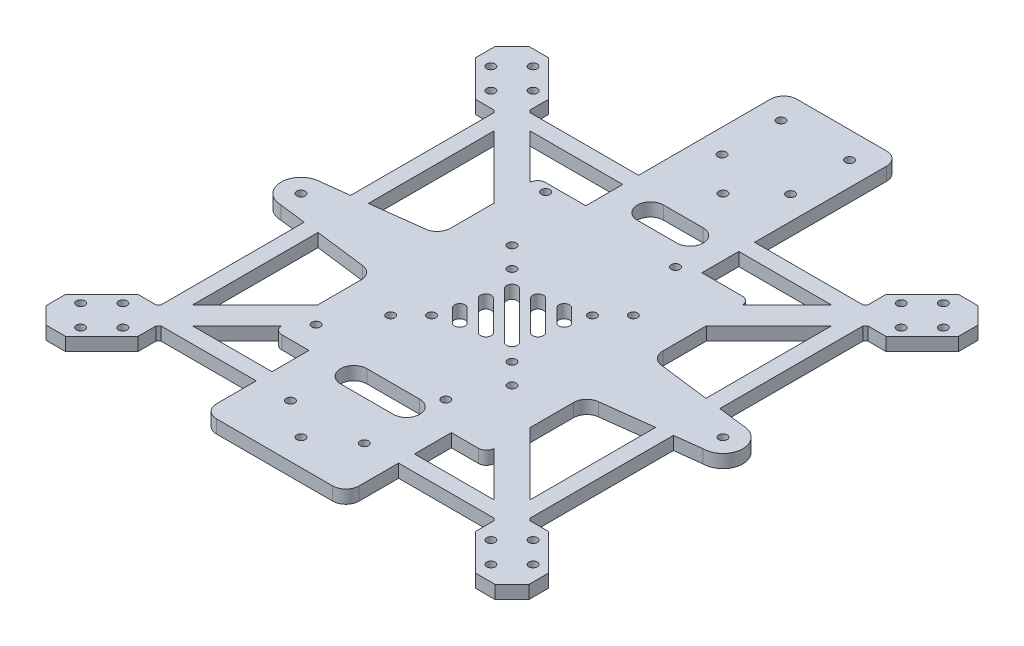
SolidWorks part; units mm, degrees
material "3k碳纤维板"
ref_plane "前视基准面" through (0, 0, 0) normal (0, 0, 1) x (1, 0, 0)
ref_plane "上视基准面" through (0, 0, 0) normal (0, 1, 0) x (1, 0, 0)
ref_plane "右视基准面" through (0, 0, 0) normal (1, 0, 0) x (0, 0, -1)
other "Configuration Table"
sketch "草图1" plane through (0, 0, 0) normal (0, 1, 0) x (1, 0, 0)
  line L0 (-40.28, 0) -> (40.28, 0) construction
  line L1 (-40.28, -50) -> (40.28, -50)
  line L2 (-40.28, -50) -> (-40.28, -16.9164)
  line L3 (-40.28, 50) -> (40.28, 50)
  line L4 (40.28, -50) -> (40.28, -16.9164)
  line L5 (-40.28, -50) -> (40.28, 50) construction
  line L6 (-40.28, 50) -> (40.28, -50) construction
  line L7 (0, -50) -> (0, 50) construction
  line L8 (-40.28, -50) -> (-40.28, -90) construction
  line L9 (-40.28, -90) -> (40.28, -90) construction
  line L10 (40.28, -90) -> (40.28, -50) construction
  line L11 (0, -50) -> (0, -90) construction
  line L12 (-40.28, -70) -> (40.28, -70) construction
  line L13 (-27, -90) -> (27, -90)
  line L14 (27, -90) -> (27, -50)
  line L15 (-27, -90) -> (-27, -50)
  line L16 (44.6626, 11.9547) -> (80, 7.5578)
  line L17 (44.6626, -11.9547) -> (80, -7.5578)
  line L18 (-44.6626, -11.9547) -> (-80, -7.5578)
  line L19 (-44.6626, 11.9547) -> (-80, 7.5578)
  line L20 (40.28, 16.9164) -> (40.28, 50)
  line L21 (-40.28, 16.9164) -> (-40.28, 50)
  circle A0 centre (-34.12, 46.89) radius 1.6
  circle A1 centre (15.09, 46.89) radius 1.6
  circle A2 centre (15.09, -40.19) radius 1.6
  circle A3 centre (-34.12, -40.19) radius 1.6
  circle A5 centre (-15.25, 15.25) radius 1.6
  circle A6 centre (15.25, 15.25) radius 1.6
  circle A7 centre (15.25, -15.25) radius 1.6
  circle A8 centre (-15.25, -15.25) radius 1.6
  circle A9 centre (14, -70) radius 1.6
  circle A10 centre (-14, -70) radius 1.6
  circle A11 centre (80, 0) radius 7.5 construction
  circle A12 centre (-80, 0) radius 7.5 construction
  circle A14 centre (80, 0) radius 1.6
  circle A16 centre (-80, 0) radius 1.6
  arc A17 (80, 7.5578) -> (80, -7.5578) centre (80, 0) cw
  arc A18 (-80, 7.5578) -> (-80, -7.5578) centre (-80, 0) ccw
  arc A19 (44.6626, 11.9547) -> (40.28, 16.9164) centre (45.28, 16.9164) cw
  arc A20 (44.6626, -11.9547) -> (40.28, -16.9164) centre (45.28, -16.9164) ccw
  arc A21 (-44.6626, -11.9547) -> (-40.28, -16.9164) centre (-45.28, -16.9164) cw
  arc A22 (-44.6626, 11.9547) -> (-40.28, 16.9164) centre (-45.28, 16.9164) ccw
  point P0 (0, 0)
  point P19 (0, 0)
  point P22 (0, 0)
  point P40 (0, -90)
  point P62 (40.28, 12.5)
  point P65 (40.28, -12.5)
  point P68 (-40.28, -12.5)
  point P71 (-40.28, 12.5)
  dimension "D3" = 3.2
  dimension "D10" = 3.2
  dimension "D11" = 30.5
  dimension "D12" = 30.5
  dimension "D14" = 3.2
  dimension "D18" = 15
  dimension "D21" = 3.2
  dimension "D19" = 160
  dimension "D23" = 5
  dimension "D1" = 80.56
  dimension "D2" = 100
  dimension "D4" = 6.16
  dimension "D5" = 3.11
  dimension "D8" = 49.21
  dimension "D9" = 87.08
  dimension "D13" = 40
  dimension "D15" = 28
  dimension "D16" = 54
  dimension "D17" = 25
  dimension "D6" = 2
  dimension "D7" = 2
extrude "凸台-拉伸1" add sketch "草图1" along normal blind 5 contours L15 L13 L14 L1 A9 A10 | L1 L4 L3 L2 A6 A5 A3 A2 A1 A0 A7 A8 region at (0.0313, 0, 0.011) region at (0, 0, 70)
sketch "草图6" plane through (0, 0, 0) normal (0, 1, 0) x (1, 0, 0)
  line L0 (0, 0) -> (50000, 0) construction
  line L1 (0, 0) -> (0, 50000) construction
  line L2 (-77.7817, 77.7817) -> (77.7817, 77.7817) construction
  line L3 (77.7817, 77.7817) -> (77.7817, -77.7817) construction
  line L4 (69.7817, 77.7817) -> (85.7817, 77.7817) construction
  line L5 (77.7817, 69.7817) -> (77.7817, 85.7817) construction
  line L6 (-77.7817, -77.7817) -> (77.7817, 77.7817) construction
  line L7 (77.7817, 91.5317) -> (64.0317, 77.7817)
  line L8 (91.5317, 77.7817) -> (77.7817, 64.0317)
  line L9 (-70.9067, 64.0317) -> (-40.28, 33.405)
  line L10 (-91.5317, -91.5317) -> (88.3498, 88.3498) construction
  line L11 (-87.5951, 87.5951) -> (77.7817, -77.7817) construction
  line L12 (40.28, -50) -> (40.28, 50)
  line L13 (40.28, 50) -> (-40.28, 50)
  line L14 (-40.28, 50) -> (-40.28, -50)
  line L15 (-40.28, -50) -> (40.28, -50)
  line L16 (-77.7817, 64.0317) -> (-70.9067, 64.0317)
  line L17 (-91.5317, 77.7817) -> (-77.7817, 64.0317)
  line L18 (-91.5317, 77.7817) -> (-91.5317, 85.1678)
  line L19 (-85.1678, 91.5317) -> (-91.5317, 85.1678)
  line L20 (-77.7817, 91.5317) -> (-85.1678, 91.5317)
  line L21 (77.7817, 91.5317) -> (85.1678, 91.5317)
  line L22 (91.5317, 77.7817) -> (91.5317, 85.1678)
  line L23 (-77.7817, 91.5317) -> (-64.0317, 77.7817)
  line L24 (-64.0317, 77.7817) -> (-64.0317, 70.9067)
  line L25 (72.1249, 83.4386) -> (83.4386, 72.1249) construction
  line L26 (77.7817, 64.0317) -> (70.9067, 64.0317)
  line L27 (64.0317, 77.7817) -> (64.0317, 70.9067)
  line L28 (77.7817, 64.0317) -> (70.9067, 64.0317)
  line L29 (64.0317, 77.7817) -> (64.0317, 70.9067)
  line L30 (64.0317, 70.9067) -> (40.28, 47.155)
  line L31 (70.9067, 64.0317) -> (40.28, 33.405)
  line L32 (85.1678, 91.5317) -> (91.5317, 85.1678)
  line L33 (-64.0317, 70.9067) -> (-40.28, 47.155)
  line L34 (-64.0317, -70.9067) -> (-40.28, -47.155)
  line L35 (-64.0317, -77.7817) -> (-64.0317, -70.9067)
  line L36 (-77.7817, -91.5317) -> (-64.0317, -77.7817)
  line L37 (-77.7817, -91.5317) -> (-85.1678, -91.5317)
  line L38 (-85.1678, -91.5317) -> (-91.5317, -85.1678)
  line L39 (-91.5317, -77.7817) -> (-91.5317, -85.1678)
  line L40 (-91.5317, -77.7817) -> (-77.7817, -64.0317)
  line L41 (-77.7817, -64.0317) -> (-70.9067, -64.0317)
  line L42 (-70.9067, -64.0317) -> (-40.28, -33.405)
  line L43 (70.9067, -64.0317) -> (40.28, -33.405)
  line L44 (77.7817, -64.0317) -> (70.9067, -64.0317)
  line L45 (91.5317, -77.7817) -> (77.7817, -64.0317)
  line L46 (91.5317, -77.7817) -> (91.5317, -85.1678)
  line L47 (85.1678, -91.5317) -> (91.5317, -85.1678)
  line L48 (77.7817, -91.5317) -> (85.1678, -91.5317)
  line L49 (77.7817, -91.5317) -> (64.0317, -77.7817)
  line L50 (64.0317, -77.7817) -> (64.0317, -70.9067)
  line L51 (64.0317, -70.9067) -> (40.28, -47.155)
  circle A0 centre (-77.7817, 77.7817) radius 65.9 construction
  circle A1 centre (77.7817, 77.7817) radius 65.9 construction
  circle A2 centre (-77.7817, -77.7817) radius 65.9 construction
  circle A3 centre (77.7817, -77.7817) radius 65.9 construction
  circle A4 centre (0, 0) radius 110 construction
  circle A5 centre (77.7817, 77.7817) radius 8 construction
  circle A6 centre (77.7817, 85.7817) radius 1.6
  circle A7 centre (85.7817, 77.7817) radius 1.6
  circle A8 centre (77.7817, 69.7817) radius 1.6
  circle A9 centre (69.7817, 77.7817) radius 1.6
  circle A10 centre (77.7817, 77.7817) radius 13.75 construction
  circle A11 centre (-77.7817, 85.7817) radius 1.6
  circle A12 centre (-85.7817, 77.7817) radius 1.6
  circle A13 centre (-69.7817, 77.7817) radius 1.6
  circle A14 centre (-77.7817, 69.7817) radius 1.6
  circle A15 centre (-77.7817, -69.7817) radius 1.6
  circle A16 centre (-69.7817, -77.7817) radius 1.6
  circle A17 centre (-85.7817, -77.7817) radius 1.6
  circle A18 centre (-77.7817, -85.7817) radius 1.6
  circle A19 centre (77.7817, -85.7817) radius 1.6
  circle A20 centre (85.7817, -77.7817) radius 1.6
  circle A21 centre (69.7817, -77.7817) radius 1.6
  circle A22 centre (77.7817, -69.7817) radius 1.6
  point P18 (77.7817, 77.7817)
  point P21 (77.7817, 77.7817)
  point P24 (0, 0)
  point P31 (77.7817, 77.7817)
  point P77 (77.7817, 77.7817)
  dimension "D1" = 3.2
  dimension "D2" = 3.2
  dimension "D3" = 3.2
  dimension "D4" = 3.2
  dimension "D5" = 3.2
  dimension "D6" = 3.2
  dimension "D7" = 3.2
  dimension "D8" = 3.2
  dimension "D9" = 3.2
  dimension "D10" = 3.2
  dimension "D11" = 3.2
  dimension "D12" = 3.2
  dimension "D13" = 3.2
  dimension "D14" = 3.2
  dimension "D15" = 3.2
  dimension "D16" = 3.2
extrude "凸台-拉伸3" add sketch "草图6" along normal blind 5 contours L33 L24 L23 L20 L19 L18 L17 L16 L9 L14 A13 A11 A12 A14 | L32 L21 L7 L27 L30 L12 L31 L26 L8 L22 A9 A8 A7 A6 | L51 L50 L49 L48 L47 L46 L45 L44 L43 L12 A21 A19 A20 A22 | L42 L41 L40 L39 L38 L37 L36 L35 L34 L14 A18 A17 A16 A15 region at (67.5211, 0, -67.3959) region at (67.5211, 0, 67.3959) region at (-67.5211, 0, -67.3959) region at (-67.5211, 0, 67.3959)
sketch "草图7" plane through (0, 0, 0) normal (0, 1, 0) x (1, 0, 0)
  line L0 (-8.8388, 8.8388) -> (8.8388, -8.8388) construction
  line L1 (-15.25, -15.25) -> (15.25, -15.25) construction
  line L2 (-15.25, -15.25) -> (-15.25, 15.25) construction
  line L3 (-15.25, 15.25) -> (15.25, 15.25) construction
  line L4 (15.25, -15.25) -> (15.25, 15.25) construction
  line L5 (-15.25, -15.25) -> (15.25, 15.25) construction
  line L6 (-15.25, 15.25) -> (15.25, -15.25) construction
  line L7 (-7.4246, 10.253) -> (10.253, -7.4246)
  line L8 (-10.253, 7.4246) -> (7.4246, -10.253)
  line L9 (-0.7071, 10.6066) -> (10.6066, -0.7071) construction
  line L10 (0.7071, 12.0208) -> (12.0208, 0.7071)
  line L11 (-2.1213, 9.1924) -> (9.1924, -2.1213)
  line L12 (7.4246, 12.3744) -> (12.3744, 7.4246) construction
  line L13 (8.8388, 13.7886) -> (13.7886, 8.8388)
  line L14 (6.0104, 10.9602) -> (10.9602, 6.0104)
  line L15 (-12.3744, -7.4246) -> (-7.4246, -12.3744) construction
  line L16 (-13.7886, -8.8388) -> (-8.8388, -13.7886)
  line L17 (-10.9602, -6.0104) -> (-6.0104, -10.9602)
  line L18 (-10.6066, 0.7071) -> (0.7071, -10.6066) construction
  line L19 (-12.0208, -0.7071) -> (-0.7071, -12.0208)
  line L20 (-9.1924, 2.1213) -> (2.1213, -9.1924)
  line L21 (0, -50) -> (0, 50) construction
  line L22 (-40.28, 50) -> (40.28, 50) construction
  line L23 (-27, -50) -> (27, -50) construction
  line L24 (-10, -50) -> (10, -50) construction
  line L25 (-10, -45) -> (10, -45)
  line L26 (-10, -55) -> (10, -55)
  arc A0 (-7.4246, 10.253) -> (-10.253, 7.4246) centre (-8.8388, 8.8388) ccw
  arc A1 (7.4246, -10.253) -> (10.253, -7.4246) centre (8.8388, -8.8388) ccw
  arc A2 (0.7071, 12.0208) -> (-2.1213, 9.1924) centre (-0.7071, 10.6066) ccw
  arc A3 (9.1924, -2.1213) -> (12.0208, 0.7071) centre (10.6066, -0.7071) ccw
  arc A4 (8.8388, 13.7886) -> (6.0104, 10.9602) centre (7.4246, 12.3744) ccw
  arc A5 (10.9602, 6.0104) -> (13.7886, 8.8388) centre (12.3744, 7.4246) ccw
  arc A6 (-13.7886, -8.8388) -> (-10.9602, -6.0104) centre (-12.3744, -7.4246) cw
  arc A7 (-6.0104, -10.9602) -> (-8.8388, -13.7886) centre (-7.4246, -12.3744) cw
  arc A8 (-12.0208, -0.7071) -> (-9.1924, 2.1213) centre (-10.6066, 0.7071) cw
  arc A9 (2.1213, -9.1924) -> (-0.7071, -12.0208) centre (0.7071, -10.6066) cw
  arc A10 (-10, -45) -> (-10, -55) centre (-10, -50) ccw
  arc A11 (10, -55) -> (10, -45) centre (10, -50) ccw
  circle A12 centre (0, -80) radius 1.6
  point P0 (0, 0)
  point P9 (0, 0)
  point P16 (4.9497, 4.9497)
  point P21 (9.8995, 9.8995)
  point P31 (-9.8995, -9.8995)
  point P38 (-4.9497, -4.9497)
  point P48 (0, 0)
  point P51 (0, -50)
  point P53 (0, -50)
  dimension "D3" = 4
  dimension "D7" = 2
  dimension "D9" = 5
  dimension "D11" = 3.2
  dimension "D1" = 4
  dimension "D2" = 25
  dimension "D4" = 3
  dimension "D5" = 16
  dimension "D6" = 7
  dimension "D8" = 3
  dimension "D10" = 20
  dimension "D12" = 80
extrude "切除-拉伸5" cut sketch "草图7" along normal through all contours A7 L17 A6 L16 | A9 L20 A8 L19 | L8 A1 L7 A0 | L11 A3 L10 A2 | L14 A5 L13 A4 | L26 A11 L25 A10 | A12 region at (0, 0, 0) region at (4.9497, 0, -4.9497) region at (9.8995, 0, -9.8995) region at (-9.8995, 0, 9.8995) region at (-4.9497, 0, 4.9497) region at (0, 0, 50) region at (0, 0, 80)
sketch "草图8" plane through (0, 0, 0) normal (0, 1, 0) x (1, 0, 0)
  line L0 (0, 0) -> (0, 87.5) construction
  line L1 (-40.28, 50) -> (40.28, 50) construction
  line L2 (-22, 125) -> (22, 125)
  line L3 (-22, 125) -> (-22, 50)
  line L4 (-22, 50) -> (22, 50)
  line L5 (22, 125) -> (22, 50)
  line L6 (-22, 125) -> (22, 50) construction
  line L7 (-22, 50) -> (22, 125) construction
  line L8 (13, 50) -> (13, 125) construction
  line L9 (-7.5, 60) -> (7.5, 60) construction
  line L10 (-7.5, 65) -> (7.5, 65)
  line L11 (-7.5, 55) -> (7.5, 55)
  circle A0 centre (13, 115) radius 1.6
  circle A1 centre (-13, 115) radius 1.6
  circle A2 centre (13, 92.63) radius 1.6
  circle A3 centre (-13, 92.63) radius 1.6
  arc A4 (-7.5, 65) -> (-7.5, 55) centre (-7.5, 60) ccw
  arc A5 (7.5, 55) -> (7.5, 65) centre (7.5, 60) ccw
  circle A6 centre (0, 80) radius 1.6
  point P21 (0, 60)
  dimension "D4" = 3.2
  dimension "D6" = 3.2
  dimension "D9" = 5
  dimension "D11" = 3.2
  dimension "D12" = 80
  dimension "D1" = 75
  dimension "D2" = 44
  dimension "D3" = 9
  dimension "D5" = 10
  dimension "D7" = 22.37
  dimension "D8" = 15
  dimension "D10" = 5
extrude "凸台-拉伸4" add sketch "草图8" along normal blind 5
fillet "圆角1" radius 5 4 edges at (-22, 2.5, -125) (22, 2.5, -125) (27, 2.5, 90) (-27, 2.5, 90)
fillet "圆角2" radius 3 4 edges at (-40.28, 2.5, 50) (40.28, 2.5, 50) (40.28, 2.5, -50) (-40.28, 2.5, -50)
sketch "草图9" plane through (0, 0, 0) normal (0, 1, 0) x (1, 0, 0)
  line L0 (64, 9.5486) -> (64, 57.125)
  line L1 (-57.125, -64) -> (-27, -64)
  line L2 (-64, -57.125) -> (-64, -9.5486)
  line L3 (-57.125, 64) -> (-22, 64)
  line L4 (64, -57.125) -> (64, -9.5486)
  line L5 (-64, -64) -> (64, 64) construction
  line L6 (-64, 64) -> (64, -64) construction
  line L7 (-63.125, -70) -> (-27, -70)
  line L8 (-70, -63.125) -> (-70, -8.8021)
  line L9 (-63.125, 70) -> (-22, 70)
  line L10 (70, -63.125) -> (70, -8.8021)
  line L11 (-70, -70) -> (70, 70) construction
  line L12 (-70, 70) -> (70, -70) construction
  line L13 (70, 8.8021) -> (70, 63.125)
  line L14 (22, 50) -> (22, 120) construction
  line L15 (22, 64) -> (22, 70)
  line L16 (22, 70) -> (63.125, 70)
  line L17 (22, 64) -> (57.125, 64)
  line L18 (-64, 9.5486) -> (-64, 57.125)
  line L19 (-70, 8.8021) -> (-70, 63.125)
  line L20 (27, -64) -> (57.125, -64)
  line L21 (27, -70) -> (63.125, -70)
  line L66 (-64.0317, -70.9067) -> (-40.28, -47.155)
  line L67 (-37.284, -50) -> (-27, -50)
  line L68 (-27, -50) -> (-27, -85)
  line L69 (-22, -90) -> (22, -90)
  line L70 (27, -85) -> (27, -50)
  line L71 (27, -50) -> (37.284, -50)
  line L72 (40.28, -47.155) -> (64.0317, -70.9067)
  line L73 (64.0317, -70.9067) -> (64.0317, -77.7817)
  line L74 (64.0317, -77.7817) -> (77.7817, -91.5317)
  line L75 (77.7817, -91.5317) -> (85.1678, -91.5317)
  line L76 (85.1678, -91.5317) -> (91.5317, -85.1678)
  line L77 (91.5317, -85.1678) -> (91.5317, -77.7817)
  line L78 (91.5317, -77.7817) -> (77.7817, -64.0317)
  line L79 (77.7817, -64.0317) -> (70.9067, -64.0317)
  line L80 (70.9067, -64.0317) -> (40.28, -33.405)
  line L81 (40.28, -33.405) -> (40.28, -16.9164)
  line L82 (44.6626, -11.9547) -> (80, -7.5578)
  line L83 (80, 7.5578) -> (44.6626, 11.9547)
  line L84 (40.28, 16.9164) -> (40.28, 33.405)
  line L85 (40.28, 33.405) -> (70.9067, 64.0317)
  line L86 (70.9067, 64.0317) -> (77.7817, 64.0317)
  line L87 (77.7817, 64.0317) -> (91.5317, 77.7817)
  line L88 (91.5317, 77.7817) -> (91.5317, 85.1678)
  line L89 (91.5317, 85.1678) -> (85.1678, 91.5317)
  line L90 (85.1678, 91.5317) -> (77.7817, 91.5317)
  line L91 (77.7817, 91.5317) -> (64.0317, 77.7817)
  line L92 (64.0317, 77.7817) -> (64.0317, 70.9067)
  line L93 (64.0317, 70.9067) -> (40.28, 47.155)
  line L94 (37.284, 50) -> (22, 50)
  line L95 (22, 50) -> (22, 120)
  line L96 (17, 125) -> (-17, 125)
  line L97 (-22, 120) -> (-22, 50)
  line L98 (-22, 50) -> (-37.284, 50)
  line L99 (-40.28, 47.155) -> (-64.0317, 70.9067)
  line L100 (-64.0317, 70.9067) -> (-64.0317, 77.7817)
  line L101 (-64.0317, 77.7817) -> (-77.7817, 91.5317)
  line L102 (-77.7817, 91.5317) -> (-85.1678, 91.5317)
  line L103 (-85.1678, 91.5317) -> (-91.5317, 85.1678)
  line L104 (-91.5317, 85.1678) -> (-91.5317, 77.7817)
  line L105 (-91.5317, 77.7817) -> (-77.7817, 64.0317)
  line L106 (-77.7817, 64.0317) -> (-70.9067, 64.0317)
  line L107 (-70.9067, 64.0317) -> (-40.28, 33.405)
  line L108 (-40.28, 33.405) -> (-40.28, 16.9164)
  line L109 (-44.6626, 11.9547) -> (-80, 7.5578)
  line L110 (-80, -7.5578) -> (-44.6626, -11.9547)
  line L111 (-40.28, -16.9164) -> (-40.28, -33.405)
  line L112 (-40.28, -33.405) -> (-70.9067, -64.0317)
  line L113 (-70.9067, -64.0317) -> (-77.7817, -64.0317)
  line L114 (-77.7817, -64.0317) -> (-91.5317, -77.7817)
  line L115 (-91.5317, -77.7817) -> (-91.5317, -85.1678)
  line L116 (-91.5317, -85.1678) -> (-85.1678, -91.5317)
  line L117 (-85.1678, -91.5317) -> (-77.7817, -91.5317)
  line L118 (-77.7817, -91.5317) -> (-64.0317, -77.7817)
  line L119 (-64.0317, -77.7817) -> (-64.0317, -70.9067)
  line L120 (-63.125, -70) -> (-57.125, -64)
  line L122 (-27, -64) -> (-27, -70)
  line L124 (27, -70) -> (27, -64)
  line L126 (57.125, -64) -> (63.125, -70)
  line L134 (70, -63.125) -> (64, -57.125)
  line L136 (64, -9.5486) -> (70, -8.8021)
  line L137 (70, 8.8021) -> (64, 9.5486)
  line L139 (64, 57.125) -> (70, 63.125)
  line L147 (63.125, 70) -> (57.125, 64)
  line L151 (-22, 70) -> (-22, 64)
  line L153 (-57.125, 64) -> (-63.125, 70)
  line L161 (-70, 63.125) -> (-64, 57.125)
  line L163 (-64, 9.5486) -> (-70, 8.8021)
  line L164 (-70, -8.8021) -> (-64, -9.5486)
  line L166 (-64, -57.125) -> (-70, -63.125)
  arc A14 (-40.28, -47.155) -> (-37.284, -50) centre (-37.284, -47) ccw
  arc A15 (-27, -85) -> (-22, -90) centre (-22, -85) ccw
  arc A16 (22, -90) -> (27, -85) centre (22, -85) ccw
  arc A17 (37.284, -50) -> (40.28, -47.155) centre (37.284, -47) ccw
  arc A18 (44.6626, -11.9547) -> (40.28, -16.9164) centre (45.28, -16.9164) ccw
  arc A19 (80, -7.5578) -> (80, 7.5578) centre (80, 0) ccw
  arc A20 (40.28, 16.9164) -> (44.6626, 11.9547) centre (45.28, 16.9164) ccw
  arc A21 (40.28, 47.155) -> (37.284, 50) centre (37.284, 47) ccw
  arc A22 (22, 120) -> (17, 125) centre (17, 120) ccw
  arc A23 (-17, 125) -> (-22, 120) centre (-17, 120) ccw
  arc A24 (-37.284, 50) -> (-40.28, 47.155) centre (-37.284, 47) ccw
  arc A25 (-44.6626, 11.9547) -> (-40.28, 16.9164) centre (-45.28, 16.9164) ccw
  arc A26 (-80, 7.5578) -> (-80, -7.5578) centre (-80, 0) ccw
  arc A27 (-40.28, -16.9164) -> (-44.6626, -11.9547) centre (-45.28, -16.9164) ccw
  point P0 (0, 0)
  point P6 (0, 0)
  dimension "D1" = 128
  dimension "D2" = 128
  dimension "D3" = 140
  dimension "D4" = 140
  dimension "D5" = 0
extrude "凸台-拉伸6" add sketch "草图9" along normal blind 5
sketch "草图10" plane through (0, 0, 0) normal (0, 1, 0) x (1, 0, 0)
  line L0 (-87.5578, 0) -> (87.5578, 0) construction
  line L1 (0, -125) -> (0, 125) construction
  line L2 (17, 125) -> (-17, 125) construction
  arc A0 (80, -7.5578) -> (80, 7.5578) centre (80, 0) ccw construction
  circle A1 centre (-23, 23) radius 1.6
  circle A2 centre (23, 23) radius 1.6
  circle A7 centre (-23, 23) radius 1.6
  circle A8 centre (23, 23) radius 1.6
  circle A9 centre (23, -23) radius 1.6
  circle A10 centre (-23, -23) radius 1.6
  point P3 (0, 0)
  point P7 (0, 0)
  point P13 (0, 0)
  dimension "D1" = 3.2
  dimension "D7" = 46
  dimension "D6" = 46
extrude "数传定位孔" cut sketch "草图10" along normal through all contours A1 | A2 | A9 | A10 region at (-23, 0, -23) region at (23, 0, -23) region at (23, 0, 23) region at (-23, 0, 23)
